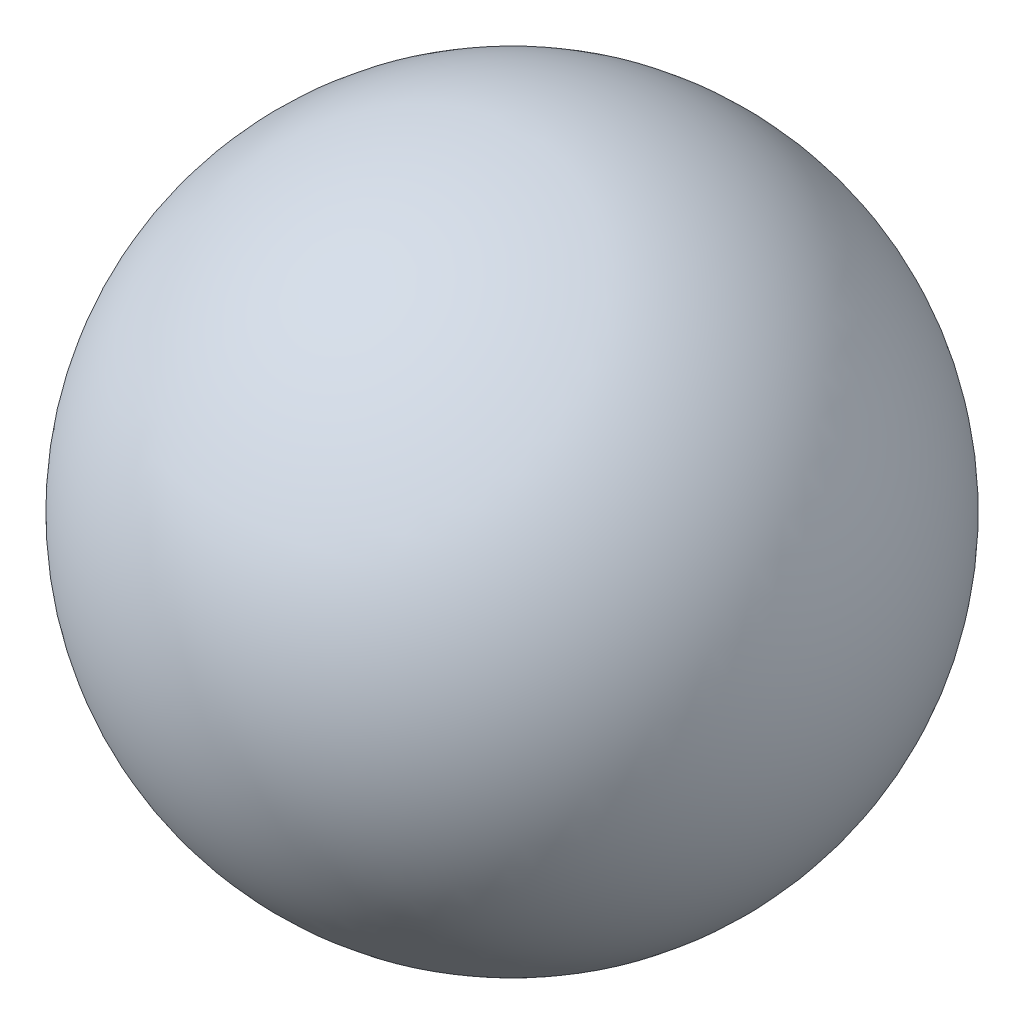
SolidWorks part; units mm, degrees
ref_plane "前视基准面" through (0, 0, 0) normal (0, 0, 1) x (1, 0, 0)
ref_plane "上视基准面" through (0, 0, 0) normal (0, 1, 0) x (1, 0, 0)
ref_plane "右视基准面" through (0, 0, 0) normal (1, 0, 0) x (0, 0, -1)
sketch "草图1" plane through (0, 0, 0) normal (0, 0, 1) x (1, 0, 0)
  line L0 (0, 124.4874) -> (0, -127.4975) construction
  line L1 (0, 108) -> (0, -108)
  arc A0 (0, -108) -> (0, 108) centre (0, 0) ccw
  dimension "D1" = 216
revolve "旋转1" add sketch "草图1" angle 360 about L0
ref_plane "基准面1" through (0, 0, 34) normal (0, 0, 1) x (1, 0, 0)
ref_axis "基准轴1" through (0, -118.8, 0) along (0, 1, 0)
ref_point "点1"
other "使用曲面切除1" [suppressed]
